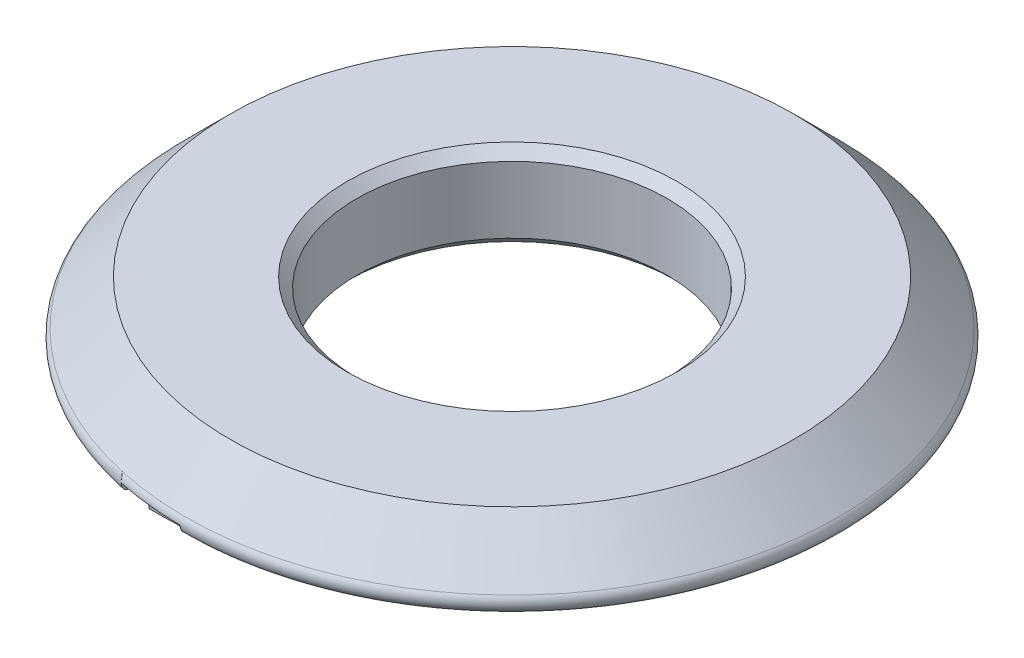
SolidWorks part; units mm, degrees
material "Markforged"
ref_plane "Front Plane" through (0, 0, 0) normal (0, 0, 1) x (1, 0, 0)
ref_plane "Top Plane" through (0, 0, 0) normal (0, 1, 0) x (1, 0, 0)
ref_plane "Right Plane" through (0, 0, 0) normal (1, 0, 0) x (0, 0, -1)
other "Bounding Box"
ref_plane "Default Plane" through (-8.9266, -12.7485, 0) normal (-0.1736, 0.9848, 0) x (0.9848, 0.1736, 0)
sketch "Sketch1" plane through (0, 0, 0) normal (1, 0, 0) x (0, 0, -1)
  line L0 (0, 0) -> (0, 8.0505) construction
  line L2 (4, 1.5875) -> (7.2644, 1.5875)
  line L3 (7.2644, 1.5875) -> (8.8519, 0)
  line L4 (8.8519, 0) -> (5.0016, 0)
  line L5 (5.0016, 0) -> (4.635, -0.635)
  line L6 (4.635, -0.635) -> (4, -0.635)
  line L8 (4, -0.635) -> (4, 1.5875)
  dimension "D1" = 7.2644
  dimension "D2" = 45
  dimension "D3" = 1.5875
  dimension "D4" = 2.2225
  dimension "D5" = 0.635
  dimension "D6" = 8
  dimension "D7" = 30
revolve "Revolve1" add sketch "Sketch1" angle 360 about L0
sketch "Sketch2" plane through (0, 0, 0) normal (0, -1, 0) x (1, 0, 0)
  line L0 (-7.1228, 5.2556) -> (7.1228, 5.2556) construction
  line L1 (0, 5.0016) -> (0, 5.2556) construction
  circle A0 centre (0, 0) radius 8.8519 construction
  circle A1 centre (0, 0) radius 5.0016 construction
  text T0 "<b>In</b>" font "Comic Sans MS" height 3.81
  dimension "D1" = 0.254
extrude "Cut-Extrude1" cut sketch "Sketch2" against normal blind 0.254
fillet "Fillet1" radius 0.254 1 edges at (1.3866, 0, -8.7426)
chamfer "Chamfer1" distance 0.254 angle 45 2 edges at (0, 1.5875, -4) (0, -0.635, -4)
